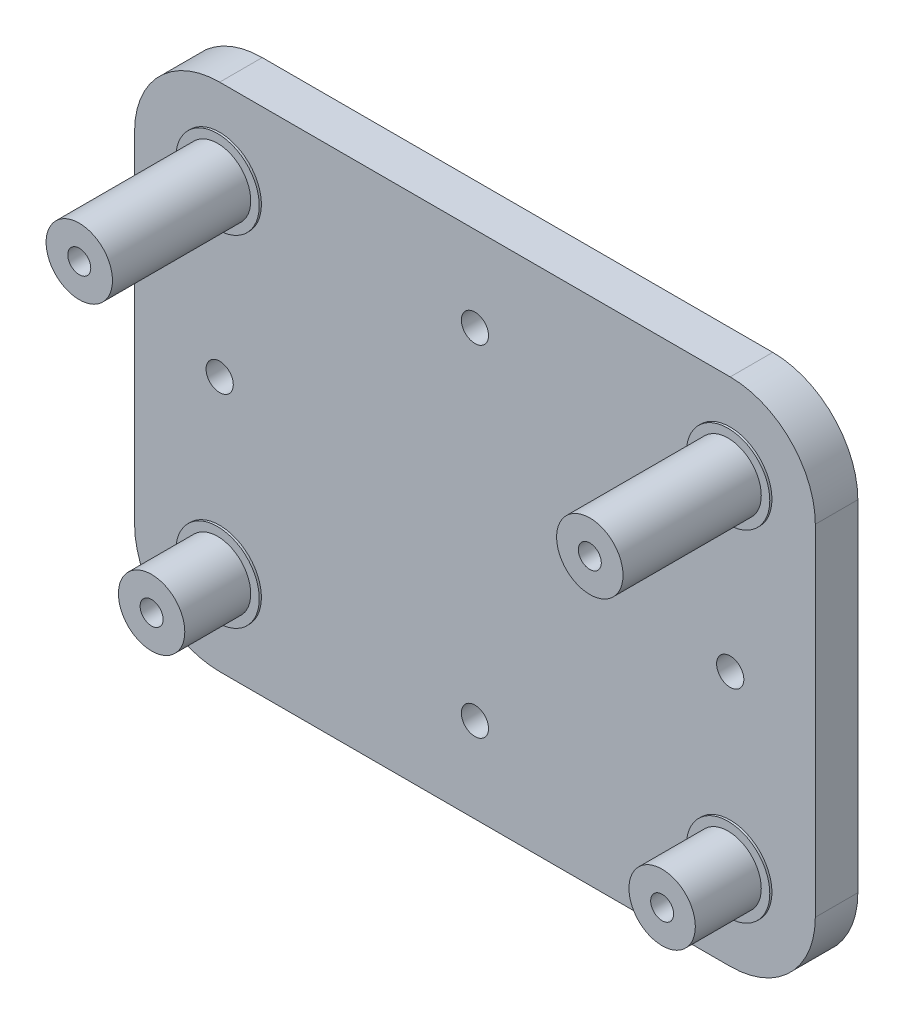
SolidWorks part; units mm, degrees
ref_plane "Front Plane" through (0, 0, 0) normal (0, 0, 1) x (1, 0, 0)
ref_plane "Top Plane" through (0, 0, 0) normal (0, 1, 0) x (1, 0, 0)
ref_plane "Right Plane" through (0, 0, 0) normal (1, 0, 0) x (0, 0, -1)
ref_axis "X" through (-88.99, 0, 0) along (1, 0, 0)
ref_axis "Y" through (0, 55, 0) along (0, -1, 0)
ref_axis "Z" through (0, 0, -88.99) along (0, 0, 1)
sketch "Sketch1" plane through (0, 0, 0) normal (0, 0, 1) x (1, 0, 0)
  line L1 (-30, 20) -> (30, 20) construction
  line L2 (-30, 20) -> (-30, -20) construction
  line L3 (-30, -20) -> (30, -20) construction
  line L4 (30, 20) -> (30, -20) construction
  line L5 (-30, 20) -> (30, -20) construction
  line L6 (-30, -20) -> (30, 20) construction
  line L7 (-40, 30) -> (40, 30)
  line L8 (-40, 30) -> (-40, -30)
  line L9 (-40, -30) -> (40, -30)
  line L10 (40, 30) -> (40, -30)
  line L11 (-40, 30) -> (40, -30) construction
  line L12 (-40, -30) -> (40, 30) construction
  circle A0 centre (-30, 20) radius 3.9
  circle A1 centre (-30, -20) radius 3.9
  circle A2 centre (30, -20) radius 3.9
  circle A3 centre (30, 20) radius 3.9
  circle A4 centre (-30, 20) radius 4.9
  circle A5 centre (30, 20) radius 4.9
  circle A6 centre (30, -20) radius 4.9
  circle A7 centre (-30, -20) radius 4.9
  circle A8 centre (-30, 20) radius 1.35
  circle A9 centre (-30, -20) radius 1.35
  circle A10 centre (30, 20) radius 1.35
  circle A11 centre (30, -20) radius 1.35
  circle A12 centre (-30, 0) radius 1.6
  circle A13 centre (0, 20) radius 1.6
  circle A14 centre (30, 0) radius 1.6
  circle A15 centre (0, -20) radius 1.6
  point P0 (0, 0)
  point P10 (0, 0)
  dimension "D1" = 40
  dimension "D3" = 7.8
  dimension "D6" = 1
  dimension "D7" = 2.7
  dimension "D8" = 3.2
  dimension "D2" = 60
  dimension "D4" = 10
  dimension "D5" = 10
extrude "Boss-Extrude1" add sketch "Sketch1" against normal blind 5 contours L8 L9 L10 L7
extrude "Boss-Extrude2" add sketch "Sketch1<3>" along normal blind 8 contours A1 A9 | A2 A11 region at (-33.7897, -20, 0) region at (26.2103, -20, 0)
sketch "Sketch1<3>" plane through (0, 0, 0) normal (0, 0, 1) x (1, 0, 0) same geometry as "Sketch1"
extrude "Boss-Extrude4" add sketch "Sketch1<5>" along normal blind 16.5 contours A0 A8 | A3 A10 region at (-33.7897, 20, 0) region at (26.2103, 20, 0)
sketch "Sketch1<5>" plane through (0, 0, 0) normal (0, 0, 1) x (1, 0, 0) same geometry as "Sketch1"
extrude "Boss-Extrude3" add sketch "Sketch1<4>" along normal blind 0.25 contours A4 A0 | A5 A3 | A6 A2 | A7 A1 region at (-34.7614, 20, 0) region at (25.2386, 20, 0) region at (25.2386, -20, 0) region at (-34.7614, -20, 0)
sketch "Sketch1<4>" plane through (0, 0, 0) normal (0, 0, 1) x (1, 0, 0) same geometry as "Sketch1"
extrude "Cut-Extrude1" cut sketch "Sketch1<6>" against normal through all both and the other way through all contours A13 | A12 | A15 | A14 region at (-30, 0, 0) region at (0, 20, 0) region at (30, 0, 0) region at (0, -20, 0)
sketch "Sketch1<6>" plane through (0, 0, 0) normal (0, 0, 1) x (1, 0, 0) same geometry as "Sketch1"
fillet "Fillet1" radius 10 4 edges at (40, 30, -2.5) (40, -30, -2.5) (-40, -30, -2.5) (-40, 30, -2.5)
